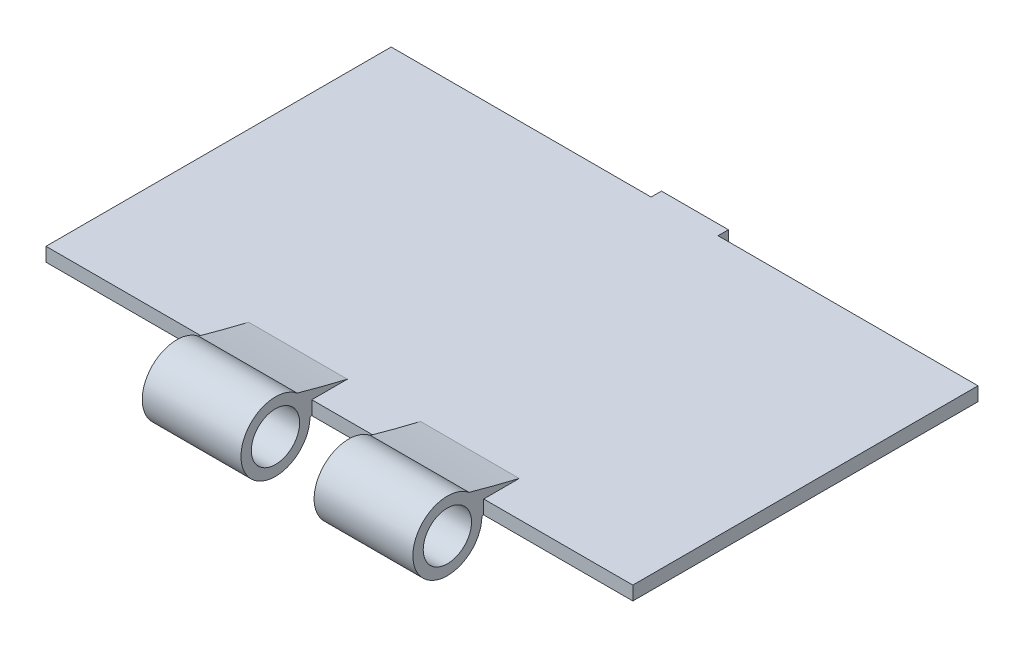
SolidWorks part; units mm, degrees
ref_plane "Plan de face" through (0, 0, 0) normal (0, 0, 1) x (1, 0, 0)
ref_plane "Plan de dessus" through (0, 0, 0) normal (0, 1, 0) x (1, 0, 0)
ref_plane "Plan de droite" through (0, 0, 0) normal (1, 0, 0) x (0, 0, -1)
sketch "Esquisse1" plane through (0, 0, 0) normal (0, 1, 0) x (1, 0, 0)
  line L1 (-42.5, 25) -> (42.5, 25)
  line L2 (-42.5, 25) -> (-42.5, -25)
  line L3 (-42.5, -25) -> (42.5, -25)
  line L4 (42.5, 25) -> (42.5, -25)
  line L5 (-42.5, 25) -> (42.5, -25) construction
  line L6 (-42.5, -25) -> (42.5, 25) construction
  point P0 (0, 0)
  dimension "D1" = 85
  dimension "D2" = 50
extrude "Boss.-Extru.1" add sketch "Esquisse1" along normal blind 2
ref_plane "Plan1" through (-18.3, 0, 0) normal (-1, 0, 0) x (0, 0, 1)
sketch "Esquisse2" plane through (-18.3, 0, 0) normal (-1, 0, 0) x (0, 0, 1)
  line L0 (25, 2) -> (25, 0) construction
  line L1 (-25, 2) -> (25, 2) construction
  line L2 (19.8455, 2) -> (25.3553, -0.0963)
  line L3 (-25, 0) -> (25, 0) construction
  circle A0 centre (30.26, 0) radius 5
  spline S0 degree 2 poles (27.1249, 3.895) (23.5046, 2.8738) (19.8455, 2) knots 0 0 0 1 1 1
  dimension "D1" = 10
  dimension "D2" = 5.26
  dimension "D3" = 0
extrude "Boss.-Extru.2" add sketch "Esquisse2" against normal blind 14.3 contours A0 S0 | A0 S0 L2 region at (-18.3, 1.9197, 23.8256) region at (-18.3, 0, 30.26)
sketch "Esquisse3" plane through (-18.3, 0, 0) normal (-1, 0, 0) x (0, 0, 1)
  circle A0 centre (30.26, 0) radius 3.5
  circle A1 centre (30.26, 0) radius 5 construction
  dimension "D1" = 0
  dimension "D2" = 7
extrude "Enlèv. mat.-Extru.1" cut sketch "Esquisse3" against normal up to surface (14.3 mm away) up to face at (-4, 0.9543, 26.8921)
pattern_linear "Répétition linéaire2" count 2 spacing 24.9 along (1, 0, 0) of "Enlèv. mat.-Extru.1", "Boss.-Extru.2"
ref_plane "Plan2" through (0, 0, 0) normal (1, 0, 0) x (0, 0, -1)
sketch "Esquisse4" plane through (0, 0, 0) normal (1, 0, 0) x (0, 0, -1)
  line L1 (25, 2) -> (26.5, 2)
  line L2 (25, 2) -> (25, -4)
  line L3 (25, -4) -> (26.5, -4)
  line L4 (26.5, 2) -> (26.5, -4)
  arc A0 (25, -4) -> (25, -2.5) centre (25, -3.25) cw
  dimension "D4" = 0.75
  dimension "D1" = 1.5
  dimension "D2" = 6
  dimension "D3" = 1.5
extrude "Boss.-Extru.3" add sketch "Esquisse4" along normal blind 4.85 and the other way blind 4.85 contours A0 L2 | L3 L4 L1 L2 region at (0, -3.25, -24.6817)
